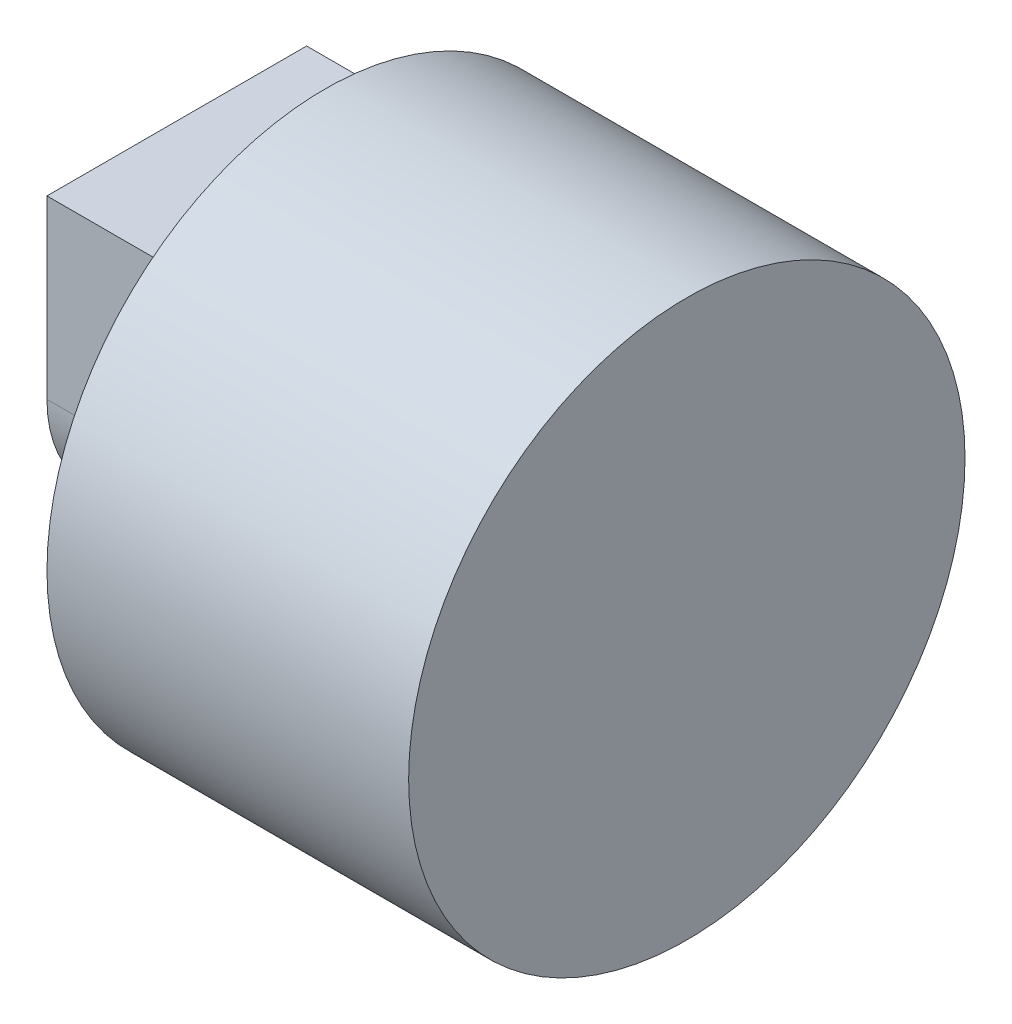
SolidWorks part; units mm, degrees
ref_plane "Front Plane" through (0, 0, 0) normal (0, 0, 1) x (1, 0, 0)
ref_plane "Top Plane" through (0, 0, 0) normal (0, 1, 0) x (1, 0, 0)
ref_plane "Right Plane" through (0, 0, 0) normal (1, 0, 0) x (0, 0, -1)
sketch "Sketch1" plane through (0, 0, 0) normal (0, 0, 1) x (1, 0, 0)
  line L0 (0, 0) -> (27.7266, 0) construction
  line L1 (0, 0) -> (0, 15)
  line L2 (0, 15) -> (19.5, 15)
  line L3 (19.5, 15) -> (19.5, 0)
  line L4 (0, 0) -> (19.5, 0)
  dimension "D1" = 19.5
  dimension "D2" = 15
revolve "Revolve1" add sketch "Sketch1" angle 360 about L0
sketch "Sketch2" plane through (0, 0, 0) normal (-1, 0, 0) x (0, 0, 1)
  line L0 (-7, 0) -> (-7, 9.5)
  line L1 (-7, 9.5) -> (7, 9.5)
  line L2 (7, 0) -> (7, 9.5)
  line L3 (-3, 0) -> (-3, 5.5)
  line L4 (-3, 5.5) -> (3, 5.5)
  line L5 (3, 0) -> (3, 5.5)
  arc A0 (-7, 0) -> (7, 0) centre (0, 0) ccw
  arc A1 (-3, 0) -> (3, 0) centre (0, 0) ccw
  point P5 (0, -7)
  point P11 (0, -3)
  dimension "D1" = 14
  dimension "D3" = 6
  dimension "D2" = 16.5
  dimension "D4" = 8.5
extrude "Boss-Extrude1" add sketch "Sketch2" along normal blind 8
sketch "Sketch3" plane through (0, 0, 0) normal (-1, 0, 0) x (0, 0, 1)
  circle A0 centre (0, 0) radius 3
extrude "Cut-Extrude1" cut sketch "Sketch3" against normal blind 10
ref_plane "Plane1" through (9.75, 0, 0) normal (-1, 0, 0) x (0, 0, 1)
